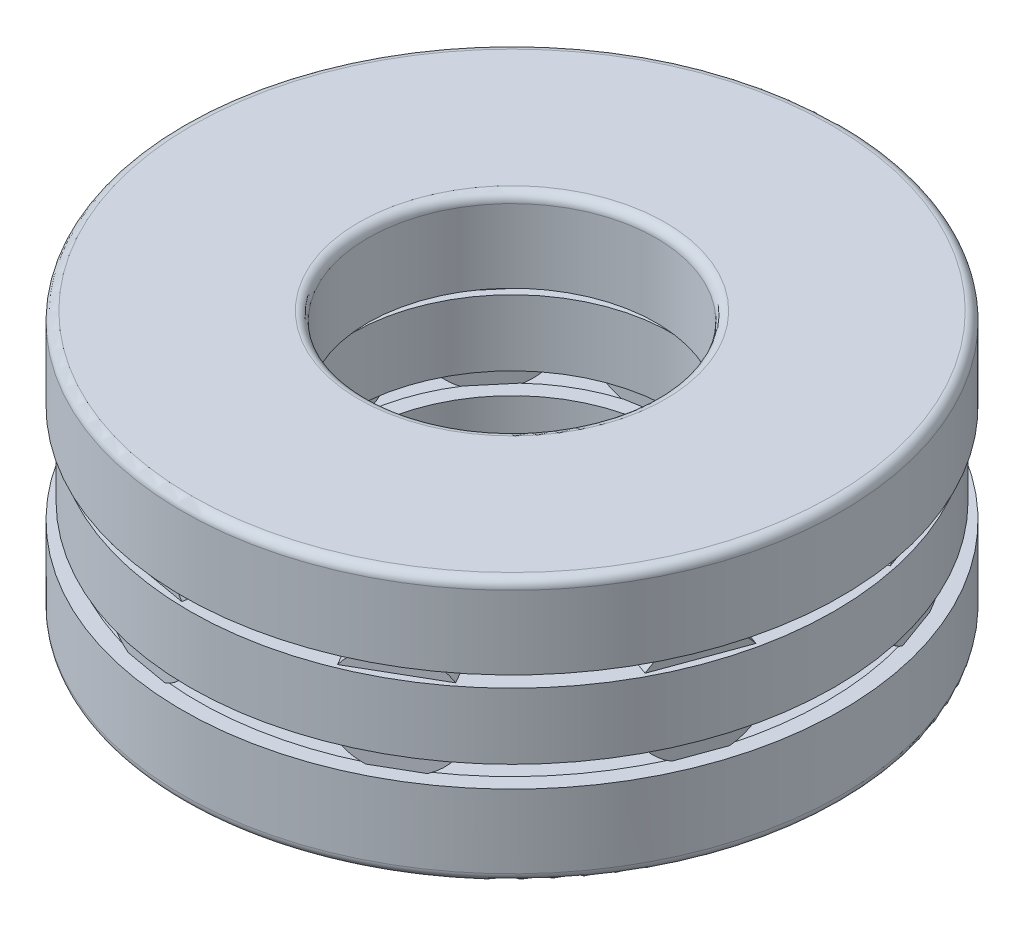
SolidWorks part; units mm, degrees
note: '?' marks a value the reader was unsure of.
ref_plane "Front" through (0, 0, 0) normal (0, 0, 1) x (1, 0, 0)
ref_plane "Top" through (0, 0, 0) normal (0, 1, 0) x (1, 0, 0)
ref_plane "Right" through (0, 0, 0) normal (1, 0, 0) x (0, 0, -1)
sketch "Support-Front-Body" plane through (0, 0, 0) normal (0, 0, 1) x (1, 0, 0)
  line L0 (-18.5, 0) -> (0, 0) construction
  line L1 (0, 16) -> (0, -16) construction
  line L2 (-18.5, -6) -> (-18.5, 6) construction
  line L3 (-40, 16) -> (-17.5, 16)
  line L4 (-40, 16) -> (-40, 6)
  line L5 (-40, 6) -> (-17.5, 6)
  line L6 (-17.5, 16) -> (-17.5, 6)
  line L7 (-40, -6) -> (-18.5, -6)
  line L8 (-40, -6) -> (-40, -16)
  line L9 (-40, -16) -> (-18.5, -16)
  line L10 (-18.5, -6) -> (-18.5, -16)
  line L11 (-34.625, 0) -> (-34.625, -16) construction
  line L12 (-23.875, 0) -> (-23.875, -16) construction
  line L18 (-29.25, 16) -> (-29.25, 6) construction
  line L19 (-29.25, 6) -> (-29.25, -6) construction
  line L20 (-29.25, -6) -> (-29.25, -16) construction
  line L22 (-40, -6) -> (-40, 6) construction
  line L23 (-40, 0) -> (-29.25, 0) construction
  line L24 (-29.25, 0) -> (-18.5, 0) construction
  dimension "Width-Total" = 32
  dimension "Diam-Outer-Upper-Ring" = 80
  dimension "Diam-Outer" = 80
  dimension "Diam-Inner-Lower-Ring" = 37
  dimension "Diam-Inner" = 35
  dimension "Dist-Ring" = 12
  dimension "Thickness-Ring" = 10
sketch "Support-Front-Roller" plane through (0, 0, 0) normal (0, 0, 1) x (1, 0, 0)
  line L0 (-24.52, 6.6) -> (-24.52, -6.6) construction
  line L2 (-38.28, 0) -> (0, 0) construction
  line L3 (-33.98, 6.6) -> (-33.98, -6.6) construction
  line L4 (-28.82, 6.6) -> (-20.22, 6.6)
  line L5 (-29.25, 6.6) -> (-29.25, 0) construction
  line L6 (-38.28, 6.6) -> (-29.68, 6.6)
  line L7 (-38.28, 6.6) -> (-38.28, -6.6)
  line L8 (-38.28, -6.6) -> (-29.68, -6.6)
  line L9 (-29.68, 6.6) -> (-29.68, -6.6)
  line L10 (-28.82, 6.6) -> (-28.82, -6.6)
  line L11 (-28.82, -6.6) -> (-20.22, -6.6)
  line L12 (-20.22, 6.6) -> (-20.22, -6.6)
  line L13 (-29.25, 6) -> (-29.25, -6) construction
  line L14 (-38.28, 6.6) -> (-39.14, 6.6) construction
  line L16 (-29.68, 6.6) -> (-28.82, 6.6) construction
  line L17 (-39.14, 6.6) -> (-40, 6.6) construction
  line L19 (-40, 16) -> (-40, 6) construction
  dimension "Length-Roller" = 8.6
  dimension "Diam-Roller" = 13.2
sketch "Support-Front-Groove" plane through (0, 0, 0) normal (0, 0, 1) x (1, 0, 0)
  line L0 (-38.28, 6.6) -> (-29.68, 6.6) construction
  line L2 (-38.1325, 6.4525) -> (-29.8275, 6.4525)
  line L3 (-38.1325, 6.4525) -> (-38.1325, -6.4525)
  line L4 (-38.1325, -6.4525) -> (-29.8275, -6.4525)
  line L6 (-29.8275, 6.4525) -> (-29.8275, -6.4525)
  line L7 (-28.6725, 6.4525) -> (-20.3675, 6.4525)
  line L8 (-28.6725, 6.4525) -> (-28.6725, -6.4525)
  line L9 (-28.6725, -6.4525) -> (-20.3675, -6.4525)
  line L12 (-20.3675, 6.4525) -> (-20.3675, -6.4525)
  line L13 (-29.8275, 6.4525) -> (-38.28, 6.6) construction
  line L14 (-38.28, 6.6) -> (-29.68, 6.6) construction
  line L17 (-38.1325, 0) -> (-29.8275, 0) construction
  line L18 (-38.28, 0) -> (0, 0) construction
  line L19 (-33.98, 6.4525) -> (-33.98, -6.4525) construction
  line L20 (-38.1325, 6.4525) -> (-38.1325, 6.6) construction
  line L21 (-38.1325, 6.4525) -> (-38.28, 6.4525) construction
  line L22 (-38.28, 6.6) -> (-38.28, -6.6) construction
  line L23 (-33.98, 6.6) -> (-33.98, -6.6) construction
  line L24 (-24.52, 6.4525) -> (-24.52, -6.4525) construction
  line L25 (-24.52, 6.6) -> (-24.52, -6.6) construction
  dimension "D1" = 1
sketch "Support-Front-Roller-Cage" plane through (0, 0, 0) normal (0, 0, 1) x (1, 0, 0)
  line L0 (-38.28, 0) -> (-19.36, 0) construction
  line L2 (-39.14, 4) -> (-19.36, 4)
  line L4 (-39.14, 4) -> (-39.14, -4)
  line L5 (-39.14, -4) -> (-19.36, -4)
  line L6 (-19.36, 4) -> (-19.36, -4)
  line L8 (-40, 0) -> (-29.25, 0) construction
  line L14 (-40, 0) -> (-39.14, 0) construction
  line L18 (-39.14, 0) -> (-38.28, 0) construction
  line L19 (-38.28, 6.6) -> (-38.28, -6.6) construction
  line L20 (-40, -6) -> (-40, 6) construction
  line L21 (-29.25, 4) -> (-29.25, 2) construction
  line L22 (-29.25, 6) -> (-29.25, -6) construction
  line L23 (-29.25, 0) -> (-29.25, 2) construction
  line L24 (-29.25, 6) -> (-29.25, 4) construction
  line L25 (-40, 6) -> (-17.5, 6) construction
ref_plane "Ref-Plane-Top" through (0, 16, 0) normal (0, 1, 0) x (-1, 0, 0)
ref_plane "Ref-Plane-Bottom" through (0, -16, 0) normal (0, 1, 0) x (-1, 0, 0)
ref_axis "Ref-Axis" through (0, -17.6, 0) along (0, 1, 0)?
sketch "Sketch6" plane through (0, 0, 0) normal (0, 0, 1) x (1, 0, 0)
  line L2 (-38.28, 0) -> (0, 0) construction
  line L3 (-38.28, 6.6) -> (-38.28, -6.6) construction
  line L5 (-29.68, 6.6) -> (-29.68, -6.6) construction
  line L6 (-38.28, 6.6) -> (-29.68, 6.6) construction
  line L7 (-38.28, 0) -> (0, 0) construction
  line L8 (-38.28, 6.6) -> (-38.28, 0)
  line L10 (-29.68, 6.6) -> (-29.68, 0)
  line L11 (-38.28, 6.6) -> (-29.68, 6.6)
  line L12 (-38.28, 0) -> (-29.68, 0)
revolve "Body-Roller" add sketch "Sketch6" angle 360 about L7
sketch "Sketch7" plane through (0, 0, 0) normal (0, 0, 1) x (1, 0, 0)
  line L0 (0, 16) -> (0, -16) construction
  line L1 (-39.14, 4) -> (-39.14, -4) construction
  line L3 (-39.14, -4) -> (-19.36, -4) construction
  line L4 (-19.36, 4) -> (-19.36, -4) construction
  line L5 (0, 16) -> (0, -16) construction
  line L7 (-39.14, 4) -> (-19.36, 4) construction
  line L9 (-39.14, 4) -> (-39.14, -4)
  line L11 (-39.14, -4) -> (-19.36, -4)
  line L12 (-19.36, 4) -> (-19.36, -4)
  line L13 (-39.14, 4) -> (-19.36, 4)
revolve "Body-Roller-Cage" add sketch "Sketch7" angle 360 about L5
sketch "Sketch10" plane through (0, 0, 0) normal (0, 0, 1) x (1, 0, 0)
  line L0 (-38.28, 0) -> (0, 0) construction
  line L1 (-28.82, 6.6) -> (-28.82, -6.6) construction
  line L3 (-20.22, 6.6) -> (-20.22, -6.6) construction
  line L4 (-28.82, 6.6) -> (-20.22, 6.6) construction
  line L5 (-28.82, 0) -> (-20.22, 0) construction
  line L6 (-28.82, 6.6) -> (-28.82, 0)
  line L7 (-20.22, 0) -> (-28.82, 0)
  line L8 (-20.22, 6.6) -> (-20.22, 0)
  line L9 (-28.82, 6.6) -> (-20.22, 6.6)
revolve "Body-Roller-2" add sketch "Sketch10" angle 360 about L5
pattern_circular "Pattern-Roller" count 9 over 360 about axis through (0, 0, 0) along (0, 1, 0) of "Body-Roller", "Body-Roller-2"
sketch "Sketch8" plane through (0, 0, 0) normal (0, 0, 1) x (1, 0, 0)
  line L4 (-20.3675, 6.4525) -> (-20.3675, -6.4525) construction
  line L5 (-28.6725, -6.4525) -> (-20.3675, -6.4525) construction
  line L6 (-28.6725, 6.4525) -> (-28.6725, -6.4525) construction
  line L7 (-29.8275, 6.4525) -> (-29.8275, -6.4525) construction
  line L8 (0, 16) -> (0, -16) construction
  line L9 (0, 16) -> (0, -16) construction
  line L10 (-38.1325, -6.4525) -> (-29.8275, -6.4525) construction
  line L11 (-38.1325, 6.4525) -> (-38.1325, -6.4525) construction
  line L12 (-40, -6) -> (-18.5, -6) construction
  line L13 (-18.5, -6) -> (-18.5, -16) construction
  line L14 (-40, -16) -> (-18.5, -16) construction
  line L15 (-40, -6) -> (-40, -16) construction
  line L16 (-20.3675, -6) -> (-20.3675, -6.4525)
  line L17 (-28.6725, -6.4525) -> (-20.3675, -6.4525)
  line L18 (-28.6725, -6) -> (-28.6725, -6.4525)
  line L19 (-29.8275, -6) -> (-29.8275, -6.4525)
  line L20 (-38.1325, -6.4525) -> (-29.8275, -6.4525)
  line L21 (-38.1325, -6) -> (-38.1325, -6.4525)
  line L22 (-40, -6) -> (-38.1325, -6)
  line L23 (-18.5, -6) -> (-18.5, -16)
  line L24 (-40, -16) -> (-18.5, -16)
  line L25 (-40, -6) -> (-40, -16)
  line L26 (-20.3675, -6) -> (-18.5, -6)
  line L27 (-29.8275, -6) -> (-28.6725, -6)
revolve "Body-Lower" add sketch "Sketch8" angle 360 about L9
sketch "Sketch9" plane through (0, 0, 0) normal (0, 0, 1) x (1, 0, 0)
  line L0 (0, 16) -> (0, -16) construction
  line L5 (0, 16) -> (0, -16) construction
  line L6 (-20.3675, 6.4525) -> (-20.3675, -6.4525) construction
  line L7 (-28.6725, 6.4525) -> (-20.3675, 6.4525) construction
  line L8 (-28.6725, 6.4525) -> (-28.6725, -6.4525) construction
  line L9 (-29.8275, 6.4525) -> (-29.8275, -6.4525) construction
  line L10 (-38.1325, 6.4525) -> (-29.8275, 6.4525) construction
  line L11 (-38.1325, 6.4525) -> (-38.1325, -6.4525) construction
  line L12 (-40, 16) -> (-40, 6) construction
  line L13 (-40, 6) -> (-17.5, 6) construction
  line L14 (-17.5, 16) -> (-17.5, 6) construction
  line L15 (-40, 16) -> (-17.5, 16) construction
  line L16 (-20.3675, 6.4525) -> (-20.3675, 6)
  line L17 (-28.6725, 6.4525) -> (-20.3675, 6.4525)
  line L18 (-28.6725, 6.4525) -> (-28.6725, 6)
  line L19 (-29.8275, 6.4525) -> (-29.8275, 6)
  line L20 (-38.1325, 6.4525) -> (-29.8275, 6.4525)
  line L21 (-38.1325, 6.4525) -> (-38.1325, 6)
  line L22 (-40, 16) -> (-40, 6)
  line L23 (-40, 6) -> (-38.1325, 6)
  line L24 (-17.5, 16) -> (-17.5, 6)
  line L25 (-40, 16) -> (-17.5, 16)
  line L26 (-20.3675, 6) -> (-17.5, 6)
  line L27 (-29.8275, 6) -> (-28.6725, 6)
revolve "Body-Upper" add sketch "Sketch9" angle 360 about L5
fillet "Cosmetic-Fillet-Outer-1" radius 1.1 1 edges at (-40, 16, 0)
fillet "Cosmetic-Fillet-Outer-2" radius 1.1 1 edges at (-40, -16, 0)
fillet "Cosmetic-Fillet-Inner-1" radius 1.1 1 edges at (-17.5, 16, 0)
fillet "Cosmetic-Fillet-Inner-2" radius 1.1 1 edges at (-18.5, -16, 0)
equation "\"Diam-Roller@Support-Front-Roller\"=\"Dist-Ring@Support-Front-Body\"*1.1"
equation "\"Num-Roller@Pattern-Roller\"=INT((PI*(\"Diam-Outer@Support-Front-Body\"-((\"Diam-Outer@Support-Front-Body\"-\"Diam-Inner@Support-Front-Body\")/2)))/(\"Diam-Roller@Support-Front-Roller\"*1.5))"
equation "\"Length-Roller@Support-Front-Roller\"= ((\"Diam-Outer@Support-Front-Body\"-\"Diam-Inner-Lower-Ring@Support-Front-Body\")/2)/2.5"
